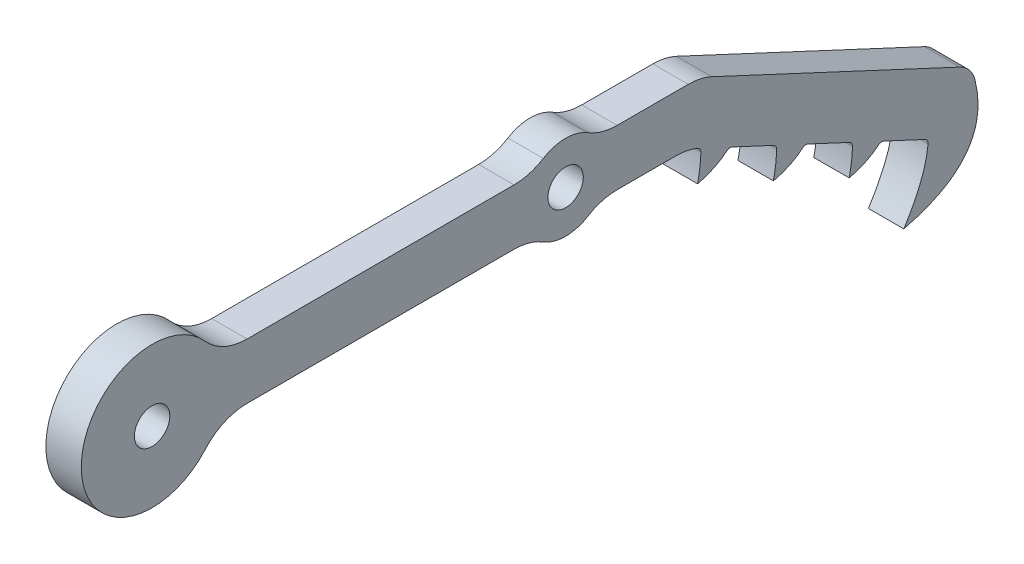
SolidWorks part; units mm, degrees
material "6061 Alloy"
ref_plane "Front Plane" through (0, 0, 0) normal (0, 0, 1) x (1, 0, 0)
ref_plane "Top Plane" through (0, 0, 0) normal (0, 1, 0) x (1, 0, 0)
ref_plane "Right Plane" through (0, 0, 0) normal (1, 0, 0) x (0, 0, -1)
sketch "Sketch1" plane through (0, 0, 0) normal (1, 0, 0) x (0, 0, -1)
  line L0 (-57.9219, 44.5435) -> (-40.0493, 54.8622)
  line L1 (-40.0493, 49.8622) -> (56.1047, 49.8622)
  line L2 (56.1047, 49.8622) -> (102.5472, 28.2057)
  line L3 (-40.0493, 59.8622) -> (58.3217, 59.8622)
  line L4 (58.3217, 59.8622) -> (106.7734, 37.2688)
  line L5 (56.1047, 49.8622) -> (84.5622, 36.5923) construction
  line L6 (58.3217, 59.8622) -> (88.7883, 45.6554) construction
  line L7 (102.5472, 28.2057) -> (106.7734, 37.2688)
  line L8 (102.5472, 28.2057) -> (111.6103, 23.9795)
  line L9 (93.4842, 32.4319) -> (106.7734, 37.2688)
  line L10 (56.1047, 49.8622) -> (58.3217, 59.8622) construction
  circle A0 centre (-57.9219, 44.5435) radius 15.875
  circle A1 centre (-40.0493, 54.8622) radius 4.7625
  circle A2 centre (-40.0493, 54.8622) radius 2.5
  circle A3 centre (-40.0493, 54.8622) radius 5
  circle A4 centre (-40.0493, 54.8622) radius 12.7
  circle A6 centre (34.1047, 54.8622) radius 7.62
  parabola Q0 (106.7734, 37.2688) -> (94.7552, 18.0752) focus (102.5472, 28.2057) apex (107.0788, 26.0926)
  parabola Q1 (99.1632, 29.7837) -> (94.7552, 18.0752) focus (93.4842, 32.4319) apex (98.5101, 34.2612)
  parabola Q2 (93.4202, 43.4955) -> (84.9631, 30.8885) focus (87.9414, 37.2725) apex (91.341, 34.5621)
  parabola Q3 (85.5686, 36.123) -> (84.9631, 30.8885) focus (78.3442, 40.2408) apex (83.762, 43.3694)
  parabola Q4 (79.8256, 49.8348) -> (71.3685, 37.2277) focus (74.3468, 43.6117) apex (77.7464, 40.9013)
  parabola Q5 (71.974, 42.4623) -> (71.3685, 37.2277) focus (64.7496, 46.58) apex (70.1674, 49.7086)
  parabola Q6 (66.2309, 56.1741) -> (57.7739, 43.567) focus (60.7522, 49.951) apex (64.1518, 47.2406)
  parabola Q7 (58.3794, 48.8015) -> (57.7739, 43.567) focus (51.155, 52.9193) apex (56.5728, 56.0479)
  point P12 (93.4842, 32.4319)
  point P19 (100.1288, 34.8504)
  point P46 (57.2132, 54.8622)
  point P47 (34.1047, 54.8622)
  dimension "D1" = 10
  dimension "D5" = 10
  dimension "D2" = 12.4745
  dimension "D3" = 5
  dimension "D4" = 15
  dimension "D6" = 5
  dimension "D7" = 22
extrude "Boss-Extrude1" add sketch "Sketch1" along normal blind 6.35 contours A0 A4 L0 A3 | L0 A4 A0 A3 | A0 A4 L1 A3 | L3 A4 A0 A3 | L0 A3 A0 | A0 A3 L0 | A3 A0 A1 | A2 A1 | A2 | L1 A4 L3 A3 | A6 L3 A4 L1 | L3 A6 L1 | L3 A6 | L1 A6 | Q6 L4 L3 A6 L1 L2 | L2 Q7 Q6 | L4 Q6 L2 Q4 | L2 Q5 Q4 | L4 Q4 L2 Q2 | L2 Q3 Q2 | L4 Q2 L2 L9 | L9 L2 L7 | Q0 L7 L8 | L2 Q1 Q0 L8 | A6 region at (0, 53.7938, 49.4225) region at (0, 47.279, 45.6612) region at (0, 52.862, 44.5166) region at (0, 51.9936, 44.0152) region at (0, 62.2646, 41.1006) region at (0, 46.6449, 36.6917) region at (0, 57.2087, 40.6781) region at (0, 53.0598, 44.5079) region at (0, 59.3323, 41.2471) region at (0, 54.8622, 31.9722) region at (0, 54.8622, 0.304) region at (0, 60.9274, -34.1047) region at (0, 54.8622, -34.1047) region at (0, 48.7971, -34.1047) region at (0, 54.2453, -53.6216) region at (0, 47.8087, -72.3396) region at (0, 46.1053, -60.0268) region at (0, 41.4694, -85.9342) region at (0, 37.45, -97.3772) region at (0, 39.7661, -73.6214) region at (0, 30.7591, -105.9447) region at (0, 32.6355, -100.9349) region at (0, 33.4268, -87.216) region at (0, 23.9786, -100.9688)
sketch "Sketch7" plane through (6.35, 0, 0) normal (1, 0, 0) x (0, 0, -1)
  point P0 (-40.0493, 54.8622)
  point P1 (34.1047, 54.8622)
hole_wizard "1/4 (0.2500) Dowel Hole4" positions "Sketch7" profile "Sketch8" hole size "1/4" standard "ANSI Inch" end condition through all
sketch "Sketch8" plane through (6.35, 54.8622, 40.0493) normal (0, 1, 0) x (0, 0, -1)
  line L0 (0, 0) -> (0, 6.35)
  line L1 (0, 6.35) -> (3.175, 6.35)
  line L2 (3.175, 6.35) -> (3.175, 0)
  line L5 (3.175, 0) -> (0, 0)
  line L11 (0, -6.35) -> (0, 107.95) construction
  dimension "Thru Hole Dia." = 6.35
  dimension "Thru Hole Depth" = 6.35
fillet "Fillet1" radius 10 2 edges at (3.175, 59.8622, 28.375) (3.175, 49.8622, 28.375)
fillet "Fillet2" radius 10 2 edges at (3.175, 49.8622, -56.1047) (3.175, 59.8622, -58.3217)
fillet "Fillet4" radius 5 1 edges at (3.175, 37.2688, -106.7734)
fillet "Fillet5" radius 1 7 edges at (3.175, 33.7664, -90.6224) (3.175, 40.1057, -77.0278) (3.175, 46.4449, -63.4331) (3.175, 48.8015, -58.3794) (3.175, 42.4623, -71.974) (3.175, 36.123, -85.5686) (3.175, 29.7837, -99.1632)
fillet "Fillet6" radius 10 4 edges at (3.175, 49.8622, -28.3545) (3.175, 49.8622, -39.8549) (3.175, 59.8622, -28.3545) (3.175, 59.8622, -39.8549)
sketch "Sketch9" plane through (6.35, 0, 0) normal (1, 0, 0) x (0, 0, -1)
  point P0 (-40.0493, 54.8622)
  point P1 (-40.0493, 62.7997)
  point P6 (-33.1752, 50.8935)
  point P7 (-46.9234, 50.8935)
  point P8 (-40.0493, 54.8622)
  dimension "D1" = 7.9375
  dimension "D2" = 3
